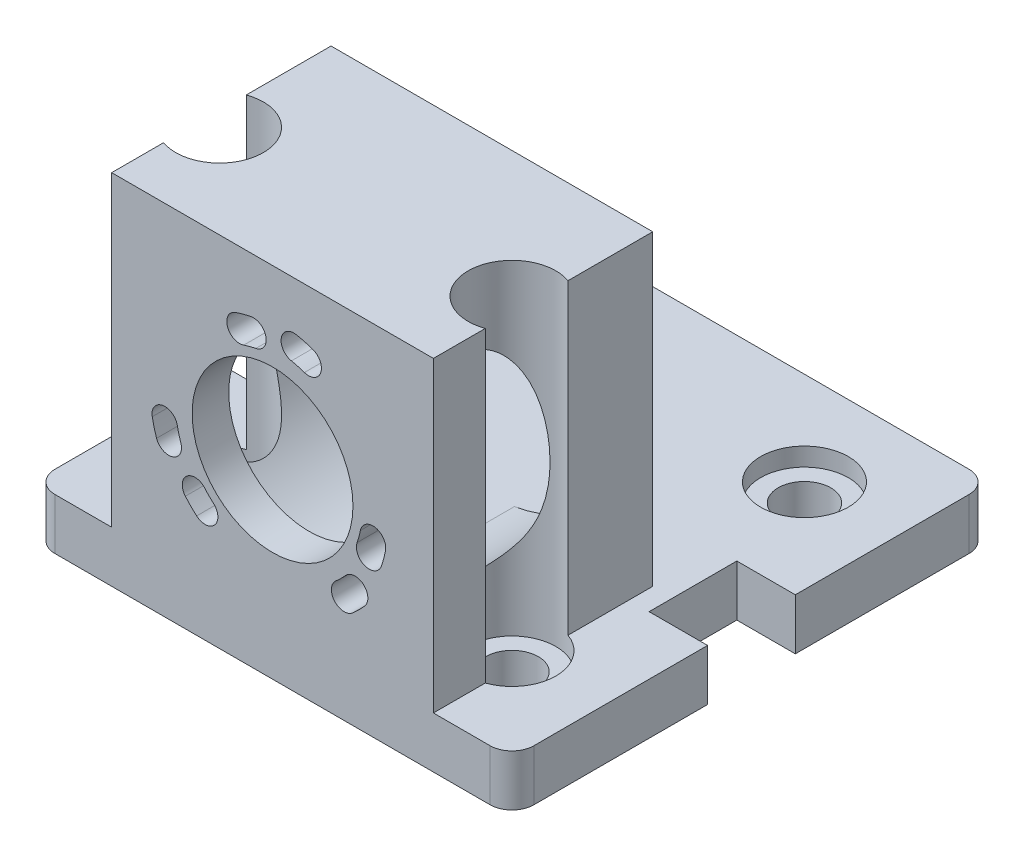
SolidWorks part; units mm, degrees
ref_plane "Front Plane" through (0, 0, 0) normal (0, 0, 1) x (1, 0, 0)
ref_plane "Top Plane" through (0, 0, 0) normal (0, 1, 0) x (1, 0, 0)
ref_plane "Right Plane" through (0, 0, 0) normal (1, 0, 0) x (0, 0, -1)
sketch "Sketch1" plane through (0, 0, 0) normal (0, 1, 0) x (1, 0, 0)
  line L5 (-29.75, 32.75) -> (29.75, 32.75)
  line L6 (-32.75, 29.75) -> (-32.75, -29.75)
  line L7 (-29.75, -32.75) -> (29.75, -32.75)
  line L8 (32.75, 29.75) -> (32.75, -29.75)
  arc A0 (29.75, -32.75) -> (32.75, -29.75) centre (29.75, -29.75) ccw
  arc A1 (-32.75, -29.75) -> (-29.75, -32.75) centre (-29.75, -29.75) ccw
  arc A2 (29.75, 32.75) -> (32.75, 29.75) centre (29.75, 29.75) cw
  arc A3 (-29.75, 32.75) -> (-32.75, 29.75) centre (-29.75, 29.75) ccw
  point P0 (0, 0)
  point P5 (0, 32.75)
  point P6 (32.75, 0)
  point P9 (32.75, -32.75)
  point P14 (32.75, 32.75)
  point P17 (-32.75, 32.75)
  dimension "D3" = 3
  dimension "D1" = 65.5
  dimension "D2" = 65.5
extrude "Boss-Extrude1" add sketch "Sketch1" along normal blind 7 contours L8 A0 L7 A1 L6 A3 L5 A2
sketch "Sketch2" plane through (0, 0, 32.75) normal (0, 0, 1) x (1, 0, 0)
  line L8 (-22, 49) -> (22, 49)
  line L9 (-22, 7) -> (22, 7)
  line L10 (-29.75, 7) -> (29.75, 7) construction
  line L11 (22, 7) -> (22, 49)
  line L14 (-22, 49) -> (-22, 7)
  line L15 (22, 7) -> (22, 49)
  circle A1 centre (0, 26) radius 11
  circle A2 centre (0, 26) radius 11
  point P13 (0, 7)
  line M16 (29.75, 7) -> (-29.75, 7)
  dimension "D3" = 11
  dimension "D1" = 44
  dimension "D2" = 42
  dimension "D4" = 19
extrude "Boss-Extrude3" add sketch "Sketch2" against normal blind 5 contours L8 L14 L11 A1 M16 region at (0, 48.3917, 32.75)
sketch "Sketch3" plane through (0, 0, 27.75) normal (0, 0, -1) x (-1, 0, 0)
  line L3 (3.0923, 7) -> (22, 7)
  line L7 (22, 49) -> (-22, 49)
  line L8 (-22, 49) -> (-22, 7)
  line L9 (-22, 7) -> (22, 7)
  line L10 (22, 7) -> (22, 49)
  line L11 (22, 49) -> (-22, 49)
  line L12 (-22, 49) -> (-22, 7)
  line L13 (-22, 7) -> (-3.0923, 7)
  line L14 (22, 7) -> (22, 49)
  arc A7 (3.0923, 7) -> (-3.0923, 7) centre (0, 26) ccw
  line M70 (22, 49) -> (-22, 49)
  line M71 (-22, 49) -> (-22, 7)
  line M72 (-22, 7) -> (22, 7)
  line M73 (22, 7) -> (22, 49)
  dimension "D1" = 38.5
  dimension "D2" = 0
extrude "Boss-Extrude4" add sketch "Sketch3" along normal blind 25 contours A7 M72 M73 M70 M71 region at (0, 45.8583, 27.75)
sketch "Sketch6" plane through (0, 0, 32.75) normal (0, 0, 1) x (1, 0, 0)
  arc A1 (12.0159, 23.6168) -> (11.5673, 21.9677) centre (0, 26) cw
  arc A2 (15.4491, 22.9358) -> (14.8723, 20.8156) centre (0, 26) cw
  arc A3 (12.0159, 23.6168) -> (15.4491, 22.9358) centre (13.7325, 23.2763) cw
  arc A4 (11.5673, 21.9677) -> (14.8723, 20.8156) centre (13.2198, 21.3916) ccw
  arc A5 (9.9667, 17.2692) -> (8.6546, 15.967) centre (0, 26) cw
  arc A6 (12.5994, 14.9629) -> (10.9407, 13.3168) centre (0, 26) cw
  arc A7 (9.9667, 17.2692) -> (12.5994, 14.9629) centre (11.283, 16.116) cw
  arc A8 (8.6546, 15.967) -> (10.9407, 13.3168) centre (9.7977, 14.6419) ccw
  arc A9 (-9.2758, 17.9986) -> (-11.926, 15.7125) centre (-10.6009, 16.8555) ccw
  arc A10 (-10.3782, 14.1528) -> (-11.926, 15.7125) centre (0, 26) cw
  arc A11 (-8.0719, 16.7855) -> (-10.3782, 14.1528) centre (-9.225, 15.4692) cw
  arc A12 (-8.0719, 16.7855) -> (-9.2758, 17.9986) centre (0, 26) cw
  arc A13 (-13.0161, 23.5214) -> (-16.4543, 22.8666) centre (-14.7352, 23.194) ccw
  arc A14 (-15.8581, 20.6071) -> (-16.4543, 22.8666) centre (0, 26) cw
  arc A15 (-12.5445, 21.734) -> (-15.8581, 20.6071) centre (-14.2013, 21.1706) cw
  arc A16 (-12.5445, 21.734) -> (-13.0161, 23.5214) centre (0, 26) cw
  arc A17 (-2.2916, 38.0338) -> (-2.9463, 41.472) centre (-2.6189, 39.7529) ccw
  arc A18 (-5.0709, 40.9114) -> (-2.9463, 41.472) centre (0, 26) cw
  arc A19 (-3.944, 37.5977) -> (-5.0709, 40.9114) centre (-4.5075, 39.2545) cw
  arc A20 (-3.944, 37.5977) -> (-2.2916, 38.0338) centre (0, 26) cw
  arc A21 (4.3615, 38.5116) -> (5.5136, 41.8165) centre (4.9375, 40.1641) ccw
  arc A22 (3.2587, 42.43) -> (5.5136, 41.8165) centre (0, 26) cw
  arc A23 (2.5778, 38.9968) -> (3.2587, 42.43) centre (2.9182, 40.7134) cw
  arc A24 (2.5778, 38.9968) -> (4.3615, 38.5116) centre (0, 26) cw
  circle A26 centre (0, 26) radius 11 construction
  point P40 (0, 26)
  dimension "D1" = 14
  dimension "D2" = 1.75
  dimension "D4" = 1.75
  dimension "D3" = 8
  dimension "D5" = 8
  dimension "D6" = 51.853
  dimension "D7" = 15
  dimension "D9" = 22
  dimension "D8" = 3
extrude "Cut-Extrude6" cut sketch "Sketch6" against normal up to surface (5 mm away) up to face at (0, 26.125, 27.75)
sketch "Sketch7" plane through (0, 7, 0) normal (0, 1, 0) x (1, 0, 0)
  line L0 (-32.75, 29.75) -> (-32.75, -29.75) construction
  line L1 (-29.75, 32.75) -> (29.75, 32.75) construction
  line L2 (-20, 20) -> (20, 20) construction
  line L3 (32.75, 29.75) -> (32.75, -29.75) construction
  line L4 (-32.75, 6) -> (-24.75, 6)
  line L5 (-32.75, 6) -> (-32.75, -6)
  line L6 (-32.75, -6) -> (-24.75, -6)
  line L7 (-24.75, 6) -> (-24.75, -6)
  line L8 (32.75, 6) -> (24.75, 6)
  line L9 (32.75, 6) -> (32.75, -6)
  line L10 (32.75, -6) -> (24.75, -6)
  line L11 (24.75, 6) -> (24.75, -6)
  circle A0 centre (-20, 20) radius 3.6
  circle A1 centre (-20, 20) radius 6
  circle A2 centre (20, 20) radius 3.6
  circle A3 centre (20, 20) radius 6
  circle A4 centre (20, -20) radius 3.6
  circle A5 centre (20, -20) radius 6
  circle A6 centre (-20, -20) radius 3.6
  circle A7 centre (-20, -20) radius 6
  point P29 (32.75, 0)
  point P30 (24.75, 0)
  point P31 (-24.75, 0)
  line M35 (-22, -32.75) -> (-22, -2.75)
  dimension "D1" = 7.2
  dimension "D2" = 12
  dimension "D7" = 8
  dimension "D8" = 8
  dimension "D3" = 12.75
  dimension "D4" = 12.75
  dimension "D6" = 40
  dimension "D9" = 12
  dimension "D10" = 12
  dimension "D12" = 2
  dimension "D5" = 2
extrude "Cut-Extrude7" cut sketch "Sketch7" against normal through all both and the other way through all contours A0 | A2 | A6 M35 | A4 | A6 | L5 L4 L7 L6 | L9 L8 L11 L10 region at (-20, 7, -20) region at (20, 7, -20) region at (-22.654, 7, 20)
extrude "Cut-Extrude9" cut sketch "Sketch7<4>" against normal blind 2.5 and the other way through all
sketch "Sketch7<4>" plane through (0, 7, 0) normal (0, 1, 0) x (1, 0, 0) same geometry as "Sketch7"
